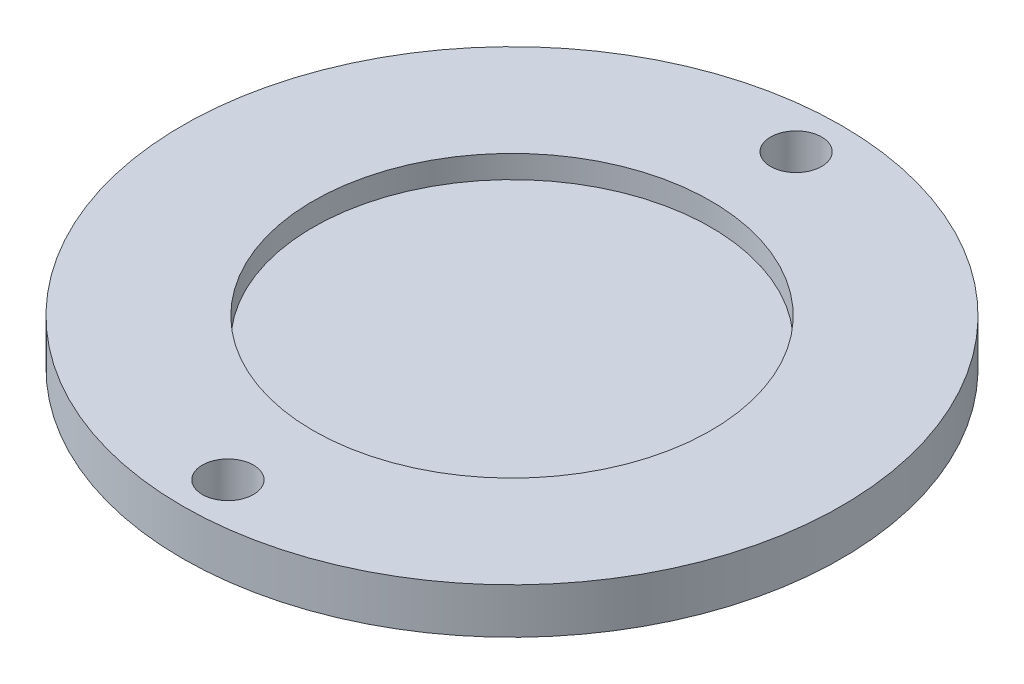
SolidWorks part; units mm, degrees
ref_plane "Front Plane" through (0, 0, 0) normal (0, 0, 1) x (1, 0, 0)
ref_plane "Top Plane" through (0, 0, 0) normal (0, 1, 0) x (1, 0, 0)
ref_plane "Right Plane" through (0, 0, 0) normal (1, 0, 0) x (0, 0, -1)
ref_axis "X" through (88.99, 0, 0) along (-1, 0, 0)
ref_axis "Y" through (0, 55, 0) along (0, -1, 0)
ref_axis "Z" through (0, 0, -88.99) along (0, 0, 1)
sketch "Sketch1" plane through (0, 0, 0) normal (0, 0, 1) x (1, 0, 0)
  line L0 (0, 0) -> (0, -21.8723) construction
  line L4 (-29, 0) -> (-29, 4)
  line L5 (-29, 4) -> (-17.5, 4)
  line L6 (-17.5, 4) -> (-17.5, 2)
  line L7 (-17.5, 2) -> (0, 2)
  line L8 (0, 2) -> (0, 0)
  line L9 (0, 0) -> (-29, 0)
  dimension "D1" = 58
  dimension "D2" = 35
  dimension "D3" = 4
  dimension "D4" = 2
revolve "Revolve1" add sketch "Sketch1" angle 360 about L0
hole_wizard "M4 Clearance Hole1" positions "Sketch2" profile "Sketch3" hole size "M4" standard "DIN" end condition up to next
sketch "Sketch2" plane through (0, 4, 0) normal (0, 1, 0) x (1, 0, 0)
  circle A0 centre (0, 0) radius 25
  point P5 (0, 25)
  point P9 (0, -25)
  dimension "D1" = 50
sketch "Sketch3" plane through (0, 4, 25) normal (1, 0, 0) x (0, 0, 1)
  line L0 (0, 0) -> (0, 4)
  line L1 (0, 4) -> (2.25, 4)
  line L2 (2.25, 4) -> (2.25, 0)
  line L5 (2.25, 0) -> (0, 0)
  line L11 (0, -6.35) -> (0, 107.95) construction
  dimension "Thru Hole Dia." = 4.5
  dimension "Thru Hole Depth" = 4
sketch "Sketch4" [suppressed] plane through (0, 1.5, 0) normal (0, 1, 0) x (1, 0, 0)
  circle A0 centre (0, 0) radius 15
  dimension "D1" = 30
extrude "Cut-Extrude1" [suppressed] cut sketch "Sketch4" against normal through all
